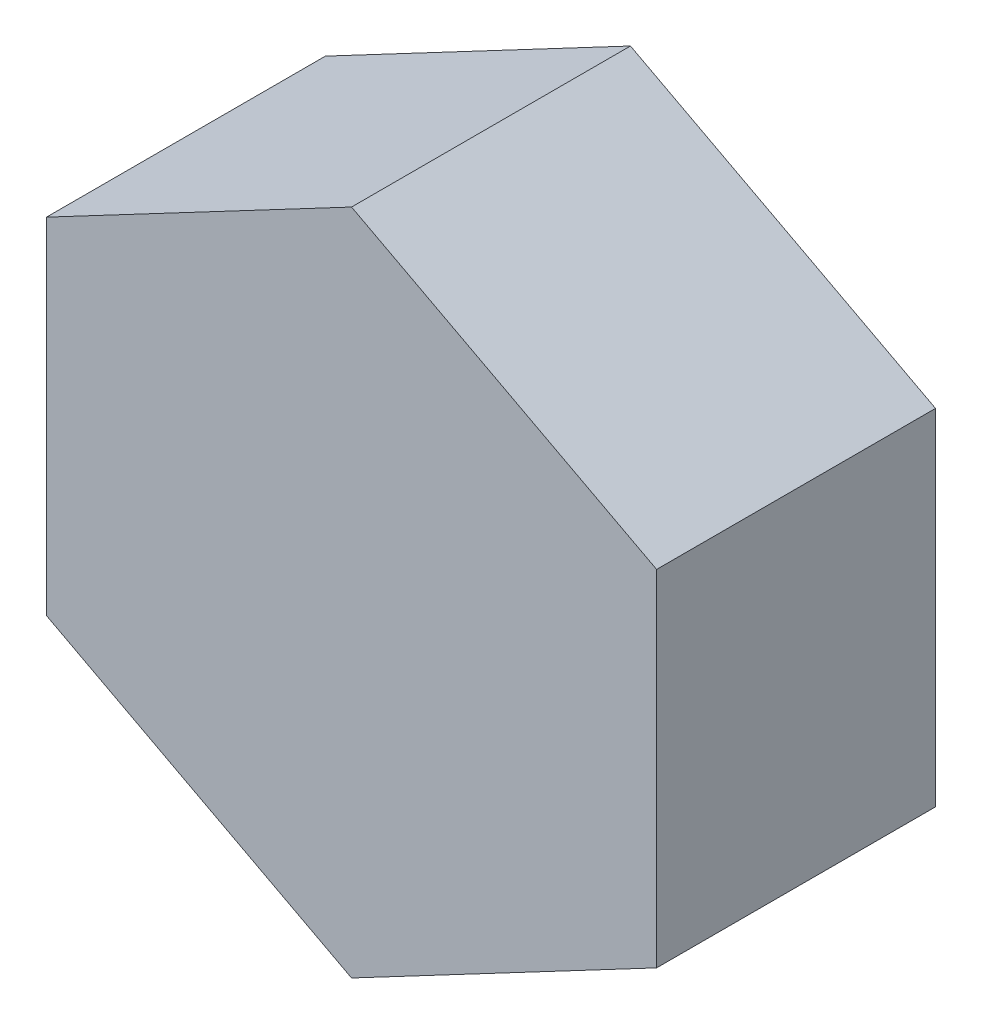
SolidWorks part; units mm, degrees
material "AISI Тип A2 Инструментальная сталь"
ref_plane "Спереди" through (0, 0, 0) normal (0, 0, 1) x (1, 0, 0)
ref_plane "Сверху" through (0, 0, 0) normal (0, 1, 0) x (1, 0, 0)
ref_plane "Справа" through (0, 0, 0) normal (1, 0, 0) x (0, 0, -1)
sketch "Эскиз1" plane through (0, 0, 0) normal (0, 0, 1) x (1, 0, 0)
  line L6 (-36.6254, 0) -> (39.3849, 0) construction
  line L7 (0, 31.7337) -> (0, -33.4897) construction
  line L9 (3.5, 1.9795) -> (0, 3.83)
  line L10 (0, 3.83) -> (-3.5, 1.9795)
  line L11 (-3.5, 1.9795) -> (-3.5, -1.9795)
  line L12 (-3.5, -1.9795) -> (0, -3.83)
  line L13 (0, -3.83) -> (3.5, -1.9795)
  line L14 (3.5, -1.9795) -> (3.5, 1.9795)
  point P4 (-3.5, 0)
  point P13 (3.5, 0)
  dimension "D1" = 7.66
  dimension "D2" = 7
extrude "Бобышка-Вытянуть1" add sketch "Эскиз1" along normal blind 3.2
